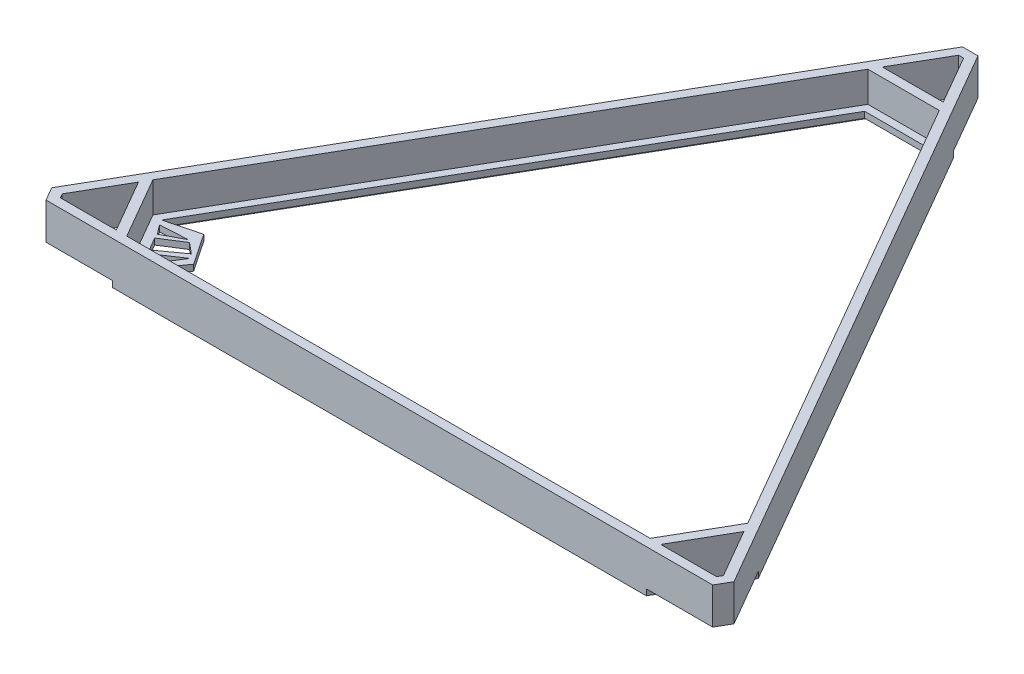
SolidWorks part; units mm, degrees
ref_plane "Front Plane" through (0, 0, 0) normal (0, 0, 1) x (1, 0, 0)
ref_plane "Top Plane" through (0, 0, 0) normal (0, 1, 0) x (1, 0, 0)
ref_plane "Right Plane" through (0, 0, 0) normal (1, 0, 0) x (0, 0, -1)
sketch "Sketch1" plane through (0, 0, 0) normal (0, 1, 0) x (1, 0, 0)
  line L17 (-4, 192.2576) -> (111, -6.9282) construction
  line L24 (4, 192.2576) -> (-111, -6.9282) construction
  line L25 (-115, 0) -> (115, 0) construction
  line L26 (0, -4.4282) -> (0, -1.4282) construction
  line L27 (-113, -3.4641) -> (-107, 0) construction
  line L28 (0, 192.2576) -> (0, 185.3294) construction
  line L29 (113, -3.4641) -> (107, 0) construction
  line L31 (-107.8246, -1.4282) -> (-108.6491, 0)
  line L39 (109.5566, -4.4282) -> (-109.5566, -4.4282)
  line L40 (-0.8246, 186.7576) -> (0.8246, 186.7576)
  line L41 (-109.5566, -4.4282) -> (-112.1132, 0)
  line L42 (-2.5566, 189.7576) -> (-112.1132, 0)
  line L43 (109.5566, -4.4282) -> (112.1132, 0)
  line L44 (-2.5566, 189.7576) -> (2.5566, 189.7576)
  line L45 (2.5566, 189.7576) -> (112.1132, 0)
  line L47 (108.6491, 0) -> (107.8246, -1.4282)
  line L50 (-99.4737, 15.8923) -> (-89.4737, -1.4282)
  line L51 (-107.8246, -1.4282) -> (-89.4737, -1.4282)
  line L52 (-99.4737, 15.8923) -> (-108.6491, 0)
  line L54 (89.4737, -1.4282) -> (107.8246, -1.4282)
  line L56 (89.4737, -1.4282) -> (99.4737, 15.8923)
  line L57 (99.4737, 15.8923) -> (108.6491, 0)
  line L58 (0, -1.4282) -> (0, 1.0718) construction
  line L59 (54.7369, 93.3788) -> (52.5718, 92.1288) construction
  line L62 (-10, 170.8653) -> (10, 170.8653)
  line L63 (-10, 170.8653) -> (-0.8246, 186.7576)
  line L64 (0.8246, 186.7576) -> (10, 170.8653)
  line L65 (94.4737, 7.2321) -> (91.8756, 8.7321) construction
  line L66 (-11.7321, 167.8653) -> (11.7321, 167.8653)
  line L67 (97.7417, 18.8923) -> (86.0096, -1.4282)
  line L68 (97.7417, 18.8923) -> (11.7321, 167.8653)
  line L69 (-54.7369, 93.3788) -> (-52.5718, 92.1288) construction
  line L70 (-84.5662, 1.0718) -> (84.5662, 1.0718)
  line L71 (-94.4737, 7.2321) -> (-91.8756, 8.7321) construction
  line L72 (-97.7417, 18.8923) -> (-86.0096, -1.4282)
  line L73 (-86.0096, -1.4282) -> (86.0096, -1.4282)
  line L74 (-97.7417, 18.8923) -> (-11.7321, 167.8653)
  line L75 (94.8549, 18.8923) -> (10.2887, 165.3653)
  line L76 (-10.2887, 165.3653) -> (-94.8549, 18.8923)
  line L77 (-91.8756, 8.7321) -> (-89.7106, 9.9821) construction
  line L79 (91.8756, 8.7321) -> (89.7106, 9.9821) construction
  line L80 (94.8549, 18.8923) -> (84.5662, 1.0718)
  line L81 (0, 167.8653) -> (0, 165.3653) construction
  line L82 (-10.2887, 165.3653) -> (10.2887, 165.3653)
  line L83 (-94.8549, 18.8923) -> (-83.8837, 21.7452)
  line L84 (-83.8837, 21.7452) -> (-77.0392, 11.5741)
  line L85 (-77.0392, 11.5741) -> (-84.5662, 1.0718)
  line L86 (-90.8811, 12.6191) -> (-88.3823, 8.3374)
  line L87 (-88.3823, 8.3374) -> (-80.3508, 14.1344)
  line L88 (-80.3508, 14.1344) -> (-83.8837, 17.0708)
  line L89 (-83.8837, 17.0708) -> (-90.8811, 12.6191)
  line L92 (-79.2571, 12.6191) -> (-87.3824, 7.2321)
  line L94 (-91.5408, 14.1344) -> (-84.8836, 17.6902)
  line L96 (-94.8549, 18.8923) -> (-84.5662, 1.0718) construction
  line L97 (-94.8549, 18.8923) -> (-93.8549, 17.1603) construction
  line L98 (-93.8549, 17.1603) -> (-84.8836, 17.6902)
  line L99 (-93.8549, 17.1603) -> (-91.5408, 14.1344)
  line L100 (-84.5662, 1.0718) -> (-85.5662, 2.8038) construction
  line L101 (-87.3824, 7.2321) -> (-85.5662, 2.8038)
  line L102 (-85.5662, 2.8038) -> (-79.2571, 12.6191)
  point P18 (0, -1.4282)
  point P41 (0, 167.8653)
  point P44 (91.8756, 8.7321)
  point P51 (-91.8756, 8.7321)
  point P55 (0, 1.0718)
  point P57 (-52.5718, 92.1288)
  point P61 (52.5718, 92.1288)
  point P65 (-89.7106, 9.9821)
  point P69 (89.7106, 9.9821)
  point P74 (0, 165.3653)
  dimension "D1" = 8
  dimension "D2" = 8
  dimension "D3" = 8
  dimension "D4" = 230
  dimension "D5" = 230
  dimension "D6" = 230
  dimension "D7" = 3
  dimension "D8" = 3
  dimension "D9" = 3
  dimension "D10" = 2.5
  dimension "D11" = 2.5
  dimension "D12" = 2.5
  dimension "D13" = 2.5
  dimension "D14" = 2.5
  dimension "D15" = 2.5
  dimension "D16" = 2
  dimension "D17" = 2
extrude "Boss-Extrude1" add sketch "Sketch1" along normal blind 12 contours L45 L43 L39 L41 L42 L44 | L74 L66 L68 L67 L73 L72 | L52 L31 L51 L50 | L57 L47 L54 L56 | L64 L62 L63 L40
extrude "Boss-Extrude2" add sketch "Sketch1<4>" along normal blind 2 contours L74 L72 L73 L67 L68 L66 L76 L82 L75 L80 L70 region at (0, 0, -167.6067)
sketch "Sketch1<4>" plane through (0, 0, 0) normal (0, 1, 0) x (1, 0, 0) same geometry as "Sketch1"
sketch "Sketch2" plane through (0, 0, 0) normal (0, -1, 0) x (1, 0, 0)
  line L24 (-2.5566, -189.7576) -> (-112.1132, 0) construction
  line L25 (109.5566, 4.4282) -> (-109.5566, 4.4282) construction
  line L27 (2.5566, -189.7576) -> (112.1132, 0) construction
  line L33 (-89.4737, 1.4282) -> (-101.2058, -18.8923) construction
  line L34 (-89.4737, 1.4282) -> (-87.7417, 4.4282) construction
  line L35 (-11.7321, -167.8653) -> (11.7321, -167.8653)
  line L36 (89.4737, 1.4282) -> (87.7417, 4.4282) construction
  line L37 (99.4737, -15.8923) -> (101.2058, -18.8923) construction
  line L38 (86.0096, 1.4282) -> (97.7417, -18.8923)
  line L40 (101.2058, -18.8923) -> (87.7417, 4.4282)
  line L42 (-10, -170.8653) -> (-13.4641, -170.8653) construction
  line L43 (10, -170.8653) -> (13.4641, -170.8653) construction
  line L44 (87.7417, 4.4282) -> (-87.7417, 4.4282)
  line L45 (-97.7417, -18.8923) -> (-86.0096, 1.4282)
  line L46 (57.3349, -94.8788) -> (54.7369, -93.3788) construction
  line L47 (0, 4.4282) -> (0, 1.4282) construction
  line L48 (-87.7417, 4.4282) -> (-101.2058, -18.8923)
  line L49 (11.7321, -167.8653) -> (97.7417, -18.8923)
  line L50 (-86.0096, 1.4282) -> (86.0096, 1.4282)
  line L51 (-57.3349, -94.8788) -> (-54.7369, -93.3788) construction
  line L52 (-11.7321, -167.8653) -> (-97.7417, -18.8923)
  line L53 (-101.2058, -18.8923) -> (-13.4641, -170.8653)
  line L54 (-13.4641, -170.8653) -> (13.4641, -170.8653)
  line L55 (13.4641, -170.8653) -> (101.2058, -18.8923)
  point P66 (0, -167.8653)
  point P68 (-91.8756, -8.7321)
  point P72 (54.7369, -93.3788)
  point P75 (0, 1.4282)
  point P80 (-54.7369, -93.3788)
  dimension "D4" = 3
  dimension "D5" = 3
  dimension "D6" = 3
extrude "Boss-Extrude3" add sketch "Sketch2" along normal blind 2
